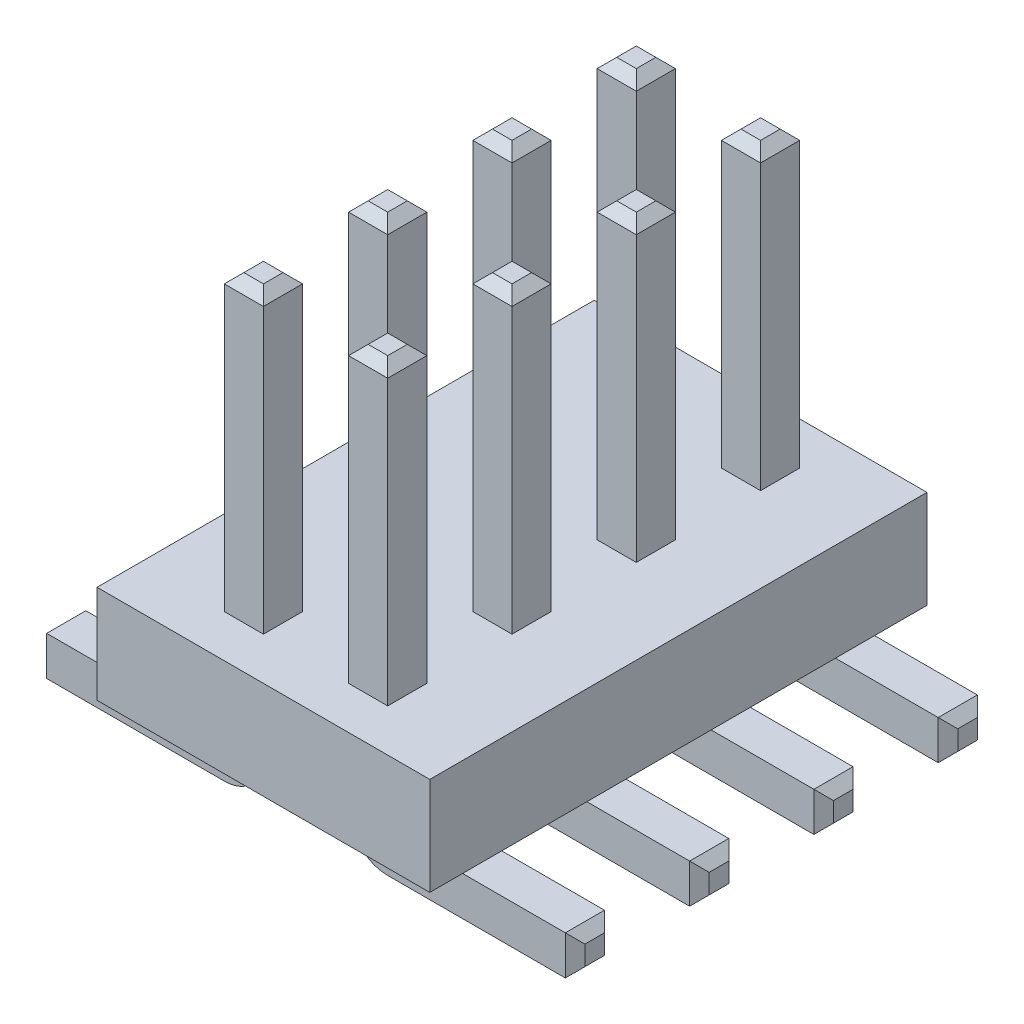
SolidWorks part; units mm, degrees
ref_plane "Vorne" through (0, 0, 0) normal (0, 0, 1) x (1, 0, 0)
ref_plane "Oben" through (0, 0, 0) normal (0, 1, 0) x (1, 0, 0)
ref_plane "Rechts" through (0, 0, 0) normal (1, 0, 0) x (0, 0, -1)
sketch "Skizze1" plane through (0, 0, 0) normal (0, 0, 1) x (1, 0, 0)
  line L1 (0, 0) -> (3.4, 0)
  line L2 (0, 0) -> (0, 1)
  line L3 (0, 1) -> (3.4, 1)
  line L4 (3.4, 0) -> (3.4, 1)
  dimension "D1" = 3.4
  dimension "D2" = 1
extrude "Aufsatz-Linear austragen1" add sketch "Skizze1" along normal blind 1.27
sketch "Skizze3" plane through (0, 0, 0) normal (0, -1, 0) x (1, 0, 0)
  line L28 (0.865, 0.435) -> (1.265, 0.435)
  line L29 (0.865, 0.435) -> (0.865, 0.835)
  line L30 (0.865, 0.835) -> (1.265, 0.835)
  line L31 (1.265, 0.435) -> (1.265, 0.835)
  line L32 (0.865, 0.435) -> (1.265, 0.835) construction
  line L33 (0.865, 0.835) -> (1.265, 0.435) construction
  line L34 (2.135, 0.435) -> (2.535, 0.435)
  line L35 (2.135, 0.435) -> (2.135, 0.835)
  line L36 (2.135, 0.835) -> (2.535, 0.835)
  line L37 (2.535, 0.435) -> (2.535, 0.835)
  line L38 (2.135, 0.435) -> (2.535, 0.835) construction
  line L39 (2.135, 0.835) -> (2.535, 0.435) construction
  line L40 (0.865, 2.975) -> (1.265, 2.975)
  line L41 (0.865, 2.975) -> (0.865, 3.375)
  line L42 (0.865, 3.375) -> (1.265, 3.375)
  line L43 (1.265, 2.975) -> (1.265, 3.375)
  line L44 (2.135, 2.975) -> (2.535, 2.975)
  line L45 (2.135, 2.975) -> (2.135, 3.375)
  line L46 (2.135, 3.375) -> (2.535, 3.375)
  line L47 (2.535, 2.975) -> (2.535, 3.375)
  line L48 (0.865, 2.975) -> (1.265, 3.375) construction
  line L49 (0.865, 3.375) -> (1.265, 2.975) construction
  line L50 (2.135, 2.975) -> (2.535, 3.375) construction
  line L51 (2.135, 3.375) -> (2.535, 2.975) construction
  line L52 (0.865, 1.705) -> (1.265, 1.705)
  line L53 (0.865, 1.705) -> (0.865, 2.105)
  line L54 (0.865, 2.105) -> (1.265, 2.105)
  line L55 (1.265, 1.705) -> (1.265, 2.105)
  line L56 (2.135, 1.705) -> (2.535, 1.705)
  line L57 (2.135, 1.705) -> (2.135, 2.105)
  line L58 (2.135, 2.105) -> (2.535, 2.105)
  line L59 (2.535, 1.705) -> (2.535, 2.105)
  line L60 (0.865, 1.705) -> (1.265, 2.105) construction
  line L61 (0.865, 2.105) -> (1.265, 1.705) construction
  line L62 (2.135, 1.705) -> (2.535, 2.105) construction
  line L63 (2.135, 2.105) -> (2.535, 1.705) construction
  point P0 (2.335, 1.905)
  point P1 (2.335, 3.175)
  point P2 (1.065, 3.175)
  point P3 (1.065, 1.905)
  point P27 (1.065, 0.635)
  point P32 (2.335, 0.635)
extrude "Aufsatz-Linear austragen3" add sketch "Skizze3" along normal blind 0.5
sketch "Skizze4" plane through (2.535, 0, 0) normal (1, 0, 0) x (0, 0, -1)
  line L10 (-0.435, -0.5) -> (-0.435, 0) construction
  line L11 (-0.835, -0.5) -> (-0.435, -0.5)
  line L12 (-0.835, -0.5) -> (-0.835, -0.1)
  line L13 (-0.835, -0.1) -> (-0.435, -0.1)
  line L14 (-0.435, -0.5) -> (-0.435, -0.1)
  dimension "D1" = 0.4
extrude "Aufsatz-Linear austragen4" add sketch "Skizze4" along normal blind 1.915
sketch "Skizze5" plane through (0.865, 0, 0) normal (-1, 0, 0) x (0, 0, 1)
  line L9 (0.435, -0.5) -> (0.435, 0) construction
  line L10 (0.835, -0.5) -> (0.435, -0.5)
  line L11 (0.835, -0.5) -> (0.835, -0.1)
  line L12 (0.835, -0.1) -> (0.435, -0.1)
  line L13 (0.435, -0.5) -> (0.435, -0.1)
extrude "Aufsatz-Linear austragen5" add sketch "Skizze5" along normal blind 1.915
sketch "Skizze6" plane through (0, 1, 0) normal (0, 1, 0) x (1, 0, 0)
  line L0 (3.4, 0) -> (0, 0) construction
  line L1 (0.865, -0.835) -> (1.265, -0.835)
  line L2 (0.865, -0.835) -> (0.865, -0.435)
  line L3 (0.865, -0.435) -> (1.265, -0.435)
  line L4 (1.265, -0.835) -> (1.265, -0.435)
  line L5 (0.865, -0.835) -> (1.265, -0.435) construction
  line L6 (0.865, -0.435) -> (1.265, -0.835) construction
  line L7 (0, -1.27) -> (0, 0) construction
  line L8 (2.135, -0.835) -> (2.535, -0.835)
  line L9 (2.135, -0.835) -> (2.135, -0.435)
  line L10 (2.135, -0.435) -> (2.535, -0.435)
  line L11 (2.535, -0.835) -> (2.535, -0.435)
  line L12 (2.135, -0.835) -> (2.535, -0.435) construction
  line L13 (2.135, -0.435) -> (2.535, -0.835) construction
  point P0 (1.065, -0.635)
  point P11 (2.335, -0.635)
  dimension "D1" = 0.4
  dimension "D2" = 0.4
  dimension "D3" = 0.635
  dimension "D4" = 1.065
  dimension "D5" = 1
extrude "Aufsatz-Linear austragen6" add sketch "Skizze6" along normal blind 3
chamfer "Fase2" distance 0.1 angle 45 16 edges at (-1.05, -0.1, 0.635) (-1.05, -0.3, 0.835) (-1.05, -0.5, 0.635) (-1.05, -0.3, 0.435) (4.45, -0.3, 0.835) (4.45, -0.1, 0.635) (4.45, -0.3, 0.435) (4.45, -0.5, 0.635) (2.335, 4, 0.835) (2.535, 4, 0.635) (2.335, 4, 0.435) (2.135, 4, 0.635) (1.065, 4, 0.835) (1.265, 4, 0.635) (1.065, 4, 0.435) (0.865, 4, 0.635)
fillet "Verrundung1" radius 0.1 2 edges at (0.865, -0.1, 0.635) (2.535, -0.1, 0.635)
fillet "Verrundung2" radius 0.4 2 edges at (2.135, -0.5, 0.635) (1.265, -0.5, 0.635)
pattern_linear "Lineares Muster1" count 4 spacing 1.27 along (0, 0, 1) of "Aufsatz-Linear austragen1", "Aufsatz-Linear austragen3", "Aufsatz-Linear austragen4", "Aufsatz-Linear austragen5", "Aufsatz-Linear austragen6", "Fase2", "Verrundung1", "Verrundung2"
